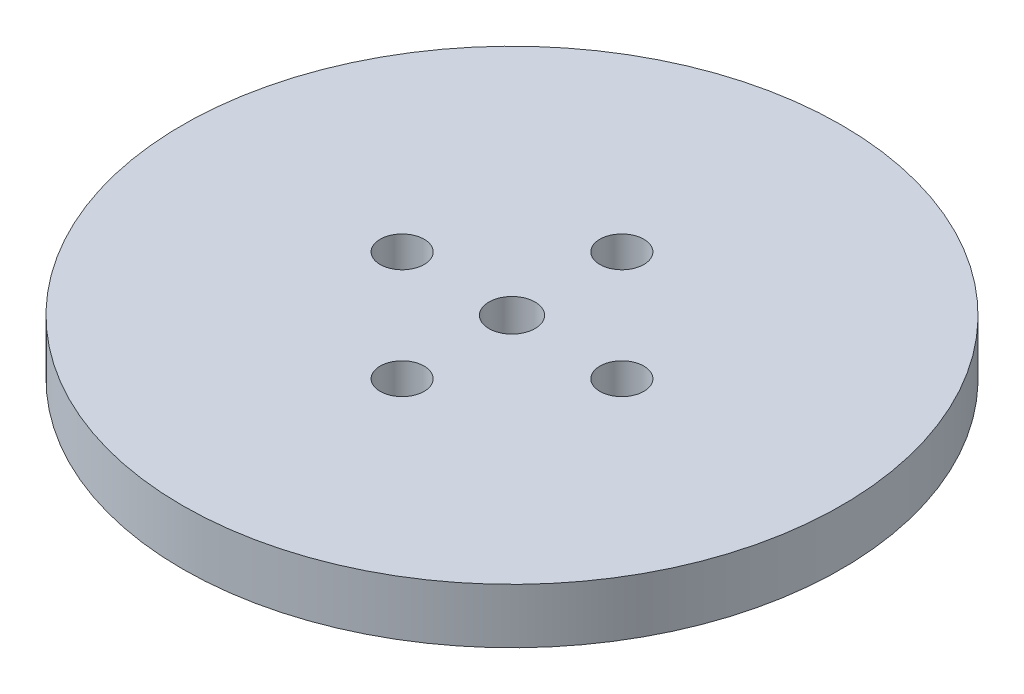
SolidWorks part; units mm, degrees
ref_plane "Front Plane" through (0, 0, 0) normal (0, 0, 1) x (1, 0, 0)
ref_plane "Top Plane" through (0, 0, 0) normal (0, 1, 0) x (1, 0, 0)
ref_plane "Right Plane" through (0, 0, 0) normal (1, 0, 0) x (0, 0, -1)
sketch "Croquis1" plane through (0, 0, 0) normal (0, 1, 0) x (1, 0, 0)
  circle A0 centre (0, 0) radius 2.05
  circle A1 centre (0, 0) radius 4
  dimension "D1" = 4.1
  dimension "D2" = 8
extrude "Saliente-Extruir1" add sketch "Croquis1" along normal blind 25.4 contours A0 | A1 A0 region at (0, 0, 0) region at (-3.8869, 0, 0)
sketch "Croquis2" plane through (0, 25.4, 0) normal (0, 1, 0) x (1, 0, 0)
  circle A1 centre (0, 0) radius 30
  dimension "D1" = 60
extrude "Saliente-Extruir2" add sketch "Croquis2" along normal blind 5 from surface starting at face at (0, 25.4, 4)
sketch "Croquis3" plane through (0, 30.4, 0) normal (0, 1, 0) x (1, 0, 0)
  circle A0 centre (0, 0) radius 10 construction
  circle A1 centre (0, 10) radius 2
  circle A2 centre (10, 0) radius 2
  circle A3 centre (0, -10) radius 2
  circle A4 centre (-10, 0) radius 2
  point P14 (0, 0)
  dimension "D1" = 20
  dimension "D2" = 4
  dimension "D5" = 20
  dimension "D4" = 10
  dimension "D3" = 4
extrude "Cortar-Extruir1" cut sketch "Croquis3" against normal blind 7.5
sketch "Croquis6" plane through (0, 0, 0) normal (0, 0, 1) x (1, 0, 0)
  circle A0 centre (0, 5) radius 1.25
  dimension "D1" = 2.5
  dimension "D2" = 5
sketch "Croquis7" plane through (0, 0, 0) normal (0, -1, 0) x (1, 0, 0)
  circle A0 centre (0, 0) radius 3.5
  dimension "D1" = 7
extrude "Cortar-Extruir3" cut sketch "Croquis7" against normal blind 3
sketch "Croquis8" plane through (0, 0, 0) normal (1, 0, 0) x (0, 0, -1)
  line L0 (-27.0724, 0) -> (-27.0724, 3)
  line L1 (-27.0724, 3) -> (35.6259, 3)
  line L2 (35.6259, 3) -> (35.6259, 0)
  line L3 (35.6259, 0) -> (-27.0724, 0)
  dimension "D1" = 3
extrude "Cortar-Extruir5" cut sketch "Croquis8" against normal mid plane 30
extrude "Cortar-Extruir6" cut sketch "Croquis1<3>" along normal blind 7.4 contours A0 region at (0, 0, 0)
sketch "Croquis1<3>" plane through (0, 0, 0) normal (0, 1, 0) x (1, 0, 0) same geometry as "Croquis1"
sketch "Croquis9" plane through (0, 3, 0) normal (0, -1, 0) x (1, 0, 0)
  line L0 (-1.2816, 1.6) -> (1.2816, 1.6)
  line L1 (0, -2.05) -> (-1.7321, -2.05) construction
  circle A0 centre (0, 0) radius 2.05 construction
  circle A1 centre (0, 0) radius 2.05
  circle M2 centre (0, 0) radius 2.05
  dimension "D2" = 4.1
  dimension "D1" = 1.6
extrude "Saliente-Extruir3" add sketch "Croquis9" against normal blind 10 contours L0 M2 region at (0, 3, 1.7818)
extrude "Cortar-Extruir7" cut sketch "Croquis6" along normal blind 10
sketch "Croquis10" plane through (0, 3, 0) normal (0, -1, 0) x (1, 0, 0)
  circle A0 centre (0, 0) radius 4.0026
extrude "Cortar-Extruir8" cut sketch "Croquis10" against normal blind 20
sketch "Croquis11" plane through (0, 30.4, 0) normal (0, 1, 0) x (1, 0, 0)
  circle A0 centre (0, 0) radius 2.1
  dimension "D1" = 4.2
extrude "Cortar-Extruir9" cut sketch "Croquis11" against normal blind 20
